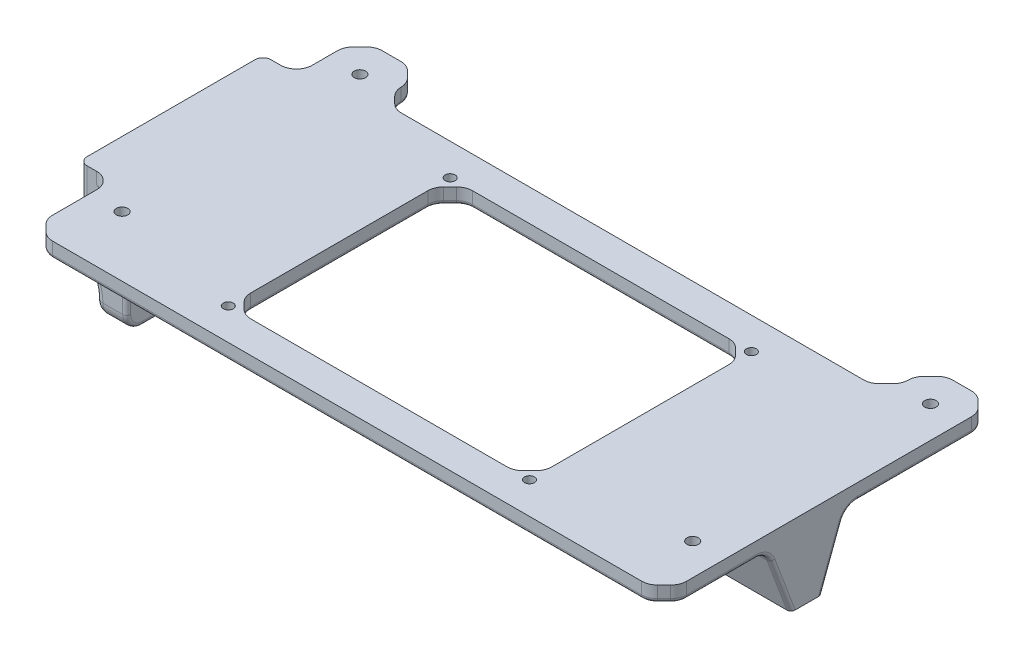
SolidWorks part; units mm, degrees
ref_plane "Front Plane" through (0, 0, 0) normal (0, 0, 1) x (1, 0, 0)
ref_plane "Top Plane" through (0, 0, 0) normal (0, 1, 0) x (1, 0, 0)
ref_plane "Right Plane" through (0, 0, 0) normal (1, 0, 0) x (0, 0, -1)
sketch "Sketch4" plane through (0, 0, 0) normal (0, 1, 0) x (1, 0, 0)
  line L1 (-47.5, 35) -> (47.5, 35) construction
  line L2 (-47.5, 35) -> (-47.5, -35) construction
  line L3 (-47.5, -35) -> (47.5, -35) construction
  line L4 (47.5, 35) -> (47.5, -35) construction
  line L5 (-100, -45) -> (100, -45)
  line L6 (-100, -45) -> (-100, 45)
  line L7 (-100, 45) -> (100, 45)
  line L8 (100, -45) -> (100, 45)
  line L9 (-100, -45) -> (100, 45) construction
  line L10 (-100, 45) -> (100, -45) construction
  point P4 (0, 0)
  dimension "D1" = 95
  dimension "D2" = 70
  dimension "D3" = 35
  dimension "D4" = 47.5
  dimension "D5" = 200
  dimension "D6" = 90
extrude "Boss-Extrude3" add sketch "Sketch4" along normal blind 5
sketch "Sketch5" plane through (0, 5, 0) normal (0, 1, 0) x (1, 0, 0)
  line L0 (-47.5, 30) -> (-42.5, 35)
  line L1 (-47.5, -35) -> (47.5, -35) construction
  line L2 (-47.5, -35) -> (-47.5, 35) construction
  line L3 (-47.5, 35) -> (47.5, 35) construction
  line L4 (47.5, -35) -> (47.5, 35) construction
  line L5 (-47.5, -35) -> (47.5, 35) construction
  line L6 (-47.5, 35) -> (47.5, -35) construction
  line L7 (-42.5, -35) -> (42.5, -35)
  line L8 (-47.5, -30) -> (-47.5, 30)
  line L9 (-42.5, 35) -> (42.5, 35)
  line L10 (47.5, -30) -> (47.5, 30)
  line L11 (-47.5, -35) -> (47.5, 35) construction
  line L12 (-47.5, 35) -> (47.5, -35) construction
  line L13 (42.5, 35) -> (47.5, 30)
  line L14 (42.5, -35) -> (47.5, -30)
  line L15 (-47.5, -30) -> (-42.5, -35)
  circle A0 centre (-47.5, 35) radius 1.575
  circle A1 centre (47.5, 35) radius 1.575
  circle A2 centre (-47.5, -35) radius 1.575
  circle A3 centre (47.5, -35) radius 1.575
  point P0 (0, 0)
  point P10 (0, 0)
  dimension "D3" = 3.15
  dimension "D4" = 3.15
  dimension "D5" = 3.15
  dimension "D6" = 3.15
  dimension "D1" = 95
  dimension "D2" = 70
extrude "Cut-Extrude1" cut sketch "Sketch5" against normal through all
sketch "Sketch6" plane through (0, 5, 0) normal (0, 1, 0) x (1, 0, 0)
  line L0 (100, 45) -> (-100, 45) construction
  line L1 (-82.55, -45) -> (82.55, -45) construction
  line L2 (-82.55, -45) -> (-82.55, 45) construction
  line L3 (-82.55, 45) -> (82.55, 45) construction
  line L4 (82.55, -45) -> (82.55, 45) construction
  line L5 (-82.55, -45) -> (82.55, 45) construction
  line L6 (-82.55, 45) -> (82.55, -45) construction
  line L7 (82.55, 0) -> (78.55, 0)
  line L8 (78.55, 0) -> (78.55, 5)
  line L9 (100, -45) -> (100, 45) construction
  line L10 (78.55, 5) -> (100, 5)
  line L11 (78.55, 5) -> (78.55, -5)
  line L12 (78.55, -5) -> (100, -5)
  line L13 (100, 5) -> (100, -5)
  point P0 (0, 0)
  dimension "D1" = 165.1
  dimension "D2" = 4
  dimension "D3" = 5
  dimension "D4" = 10
extrude "Boss-Extrude4" add sketch "Sketch6" along normal blind 20 contours L10 L13 L12 L11
sketch "Sketch8" plane through (78.55, 0, 0) normal (-1, 0, 0) x (0, 0, 1)
  line L0 (-5, 25) -> (5, 25) construction
  circle A0 centre (0, 25) radius 4
  dimension "D1" = 8
extrude "Cut-Extrude2" cut sketch "Sketch8" against normal blind 4.1
sketch "Sketch9" plane through (0, 25, 0) normal (0, 1, 0) x (1, 0, 0)
  line L0 (78.55, 0) -> (100, 0)
  line L1 (78.55, 5) -> (78.55, -5) construction
  line L2 (100, 5) -> (100, -5) construction
  circle A0 centre (87.5, 0) radius 1.8
  circle A1 centre (95, 0) radius 1.8
  dimension "D1" = 3.6
  dimension "D2" = 3.6
  dimension "D3" = 5
  dimension "D4" = 12.5
extrude "Cut-Extrude3" cut sketch "Sketch9" against normal blind 10 contours A0 | A1
sketch "Sketch10" plane through (0, 5, 0) normal (0, 1, 0) x (1, 0, 0)
  line L0 (100, 45) -> (-100, 45) construction
  line L1 (-82.55, -45) -> (82.55, -45) construction
  line L2 (-82.55, -45) -> (-82.55, 45) construction
  line L3 (-82.55, 45) -> (82.55, 45) construction
  line L4 (82.55, -45) -> (82.55, 45) construction
  line L5 (-82.55, -45) -> (82.55, 45) construction
  line L6 (-82.55, 45) -> (82.55, -45) construction
  line L7 (-82.55, 0) -> (-95.55, 0) construction
  line L8 (-95.55, 0) -> (-95.55, -38) construction
  line L10 (-95.55, -38) -> (-123.55, -38)
  line L11 (-95.55, -38) -> (-95.55, 22)
  line L12 (-95.55, 22) -> (-123.55, 22)
  line L13 (-123.55, -38) -> (-123.55, 22)
  point P0 (0, 0)
  dimension "D1" = 165.1
  dimension "D2" = 13
  dimension "D3" = 38
  dimension "D4" = 28
  dimension "D5" = 60
extrude "Boss-Extrude5" add sketch "Sketch10" along normal blind 20 contours L13 L12 L11 L10
sketch "Sketch12" plane through (0, 5, 0) normal (0, -1, 0) x (1, 0, 0)
  line L4 (-100, -22) -> (-100, 38)
  line L5 (-100, 38) -> (-123.55, 38)
  line L6 (-123.55, 38) -> (-123.55, -22)
  line L7 (-123.55, -22) -> (-100, -22)
  line L8 (-100, -22) -> (-100, 38)
  line L9 (-100, 38) -> (-123.55, 38)
  line L10 (-123.55, 38) -> (-123.55, -22)
  line L11 (-123.55, -22) -> (-100, -22)
  dimension "D1" = 0
extrude "Boss-Extrude6" add sketch "Sketch12" along normal up to surface (5 mm away) up to face at (47.5, 0, -33.425)
sketch "Sketch13" plane through (0, 25, 0) normal (0, 1, 0) x (1, 0, 0)
  line L0 (-95.55, -38) -> (-123.55, -38) construction
  line L1 (-95.55, 22) -> (-105.55, 22)
  line L2 (-95.55, 22) -> (-95.55, -38)
  line L3 (-95.55, -38) -> (-105.55, -38)
  line L4 (-105.55, 22) -> (-105.55, -38)
  dimension "D1" = 10
extrude "Boss-Extrude7" add sketch "Sketch13" along normal blind 15
sketch "Sketch14" plane through (-95.55, 0, 0) normal (1, 0, 0) x (0, 0, -1)
  line L1 (4, 25) -> (-4, 25)
  line L2 (4, 25) -> (-4, 25) construction
  line L3 (-30.5, 35.25) -> (10.5, 35.25)
  line L4 (-30.5, 35.25) -> (-30.5, 14.75)
  line L5 (-30.5, 14.75) -> (10.5, 14.75)
  line L6 (10.5, 35.25) -> (10.5, 14.75)
  arc A1 (-4, 25) -> (4, 25) centre (0, 25) ccw
  arc A2 (-4, 25) -> (4, 25) centre (0, 25) ccw construction
  dimension "D2" = 20.5
  dimension "D3" = 10.25
  dimension "D4" = 41
  dimension "D5" = 10.5
  dimension "D1" = 0
extrude "Cut-Extrude7" cut sketch "Sketch14" against normal through all contours L4 L5 L6 L3
sketch "Sketch15" plane through (0, 0, -22) normal (0, 0, -1) x (-1, 0, 0)
  line L8 (95.55, 5) -> (100, 5)
  line L9 (100, 5) -> (100, 0)
  line L10 (100, 0) -> (123.55, 0)
  line L11 (123.55, 0) -> (123.55, 25)
  line L12 (123.55, 25) -> (105.55, 25)
  line L13 (105.55, 25) -> (105.55, 40)
  line L14 (105.55, 40) -> (95.55, 40)
  line L15 (95.55, 40) -> (95.55, 5)
  line L16 (95.55, 5) -> (100, 5)
  line L17 (100, 5) -> (100, 0)
  line L18 (100, 0) -> (123.55, 0)
  line L19 (123.55, 0) -> (123.55, 25)
  line L20 (123.55, 25) -> (105.55, 25)
  line L21 (105.55, 25) -> (105.55, 40)
  line L22 (105.55, 40) -> (95.55, 40)
  line L23 (95.55, 40) -> (95.55, 5)
  dimension "D1" = 0
extrude "Cut-Extrude8" cut sketch "Sketch15" against normal blind 3
sketch "Sketch16" plane through (-95.55, 0, 0) normal (1, 0, 0) x (0, 0, -1)
  line L0 (-10, 35.25) -> (-10, 14.75) construction
  line L1 (-30.5, 35.25) -> (10.5, 35.25) construction
  line L2 (-30.5, 14.75) -> (10.5, 14.75) construction
  line L3 (-10, 25) -> (15.25, 25) construction
  line L4 (19, 5) -> (19, 40)
  line L5 (19, 40) -> (-38, 40)
  line L6 (-38, 40) -> (-38, 5)
  line L7 (-38, 5) -> (19, 5)
  line L8 (19, 5) -> (19, 40) construction
  line L9 (19, 40) -> (-38, 40) construction
  line L10 (-38, 40) -> (-38, 5) construction
  line L11 (-38, 5) -> (19, 5) construction
  line L12 (15.25, 25) -> (15.25, 30) construction
  circle A0 centre (15.25, 30) radius 1.8
  circle A1 centre (15.25, 20) radius 1.8
  circle A2 centre (-35.25, 20) radius 1.8
  circle A3 centre (-35.25, 30) radius 1.8
  dimension "D4" = 3.6
  dimension "D2" = 25.25
  dimension "D3" = 5
  dimension "D1" = 0
extrude "Cut-Extrude9" cut sketch "Sketch16" against normal blind 10
sketch "Sketch17" plane through (0, 0, 38) normal (0, 0, 1) x (1, 0, 0)
  line L8 (-100, 5) -> (-95.55, 5)
  line L9 (-95.55, 5) -> (-95.55, 40)
  line L10 (-95.55, 40) -> (-105.55, 40)
  line L11 (-105.55, 40) -> (-105.55, 25)
  line L12 (-105.55, 25) -> (-123.55, 25)
  line L13 (-123.55, 25) -> (-123.55, 0)
  line L14 (-123.55, 0) -> (-100, 0)
  line L15 (-100, 0) -> (-100, 5)
  line L16 (-100, 5) -> (-95.55, 5)
  line L17 (-95.55, 5) -> (-95.55, 40)
  line L18 (-95.55, 40) -> (-105.55, 40)
  line L19 (-105.55, 40) -> (-105.55, 25)
  line L20 (-105.55, 25) -> (-123.55, 25)
  line L21 (-123.55, 25) -> (-123.55, 0)
  line L22 (-123.55, 0) -> (-100, 0)
  line L23 (-100, 0) -> (-100, 5)
  dimension "D1" = 0
extrude "Boss-Extrude8" add sketch "Sketch17" along normal blind 1
sketch "Sketch19" plane through (-123.55, 0, 0) normal (-1, 0, 0) x (0, 0, 1)
  line L8 (-10.5, 25) -> (-19, 25)
  line L9 (-19, 25) -> (-19, 0)
  line L10 (-19, 0) -> (39, 0)
  line L11 (39, 0) -> (39, 25)
  line L12 (39, 25) -> (30.5, 25)
  line L13 (30.5, 25) -> (30.5, 14.75)
  line L14 (30.5, 14.75) -> (-10.5, 14.75)
  line L15 (-10.5, 14.75) -> (-10.5, 25)
  line L16 (-10.5, 25) -> (-19, 25)
  line L17 (-19, 25) -> (-19, 0)
  line L18 (-19, 0) -> (39, 0)
  line L19 (39, 0) -> (39, 25)
  line L20 (39, 25) -> (30.5, 25)
  line L21 (30.5, 25) -> (30.5, 14.75)
  line L22 (30.5, 14.75) -> (-10.5, 14.75)
  line L23 (-10.5, 14.75) -> (-10.5, 25)
  dimension "D1" = 0
extrude "Cut-Extrude10" cut sketch "Sketch19" against normal blind 13
fillet "Fillet1" radius 12.5 2 edges at (-105.55, 25, -14.75) (-105.55, 25, 34.75)
fillet "Fillet2" radius 5 2 edges at (-100.55, 40, 39) (-100.55, 40, -19)
fillet "Fillet3" radius 5 2 edges at (-110.55, 25, 34.75) (-110.55, 25, -14.75)
sketch "Sketch20" plane through (0, 5, 0) normal (0, 1, 0) x (1, 0, 0)
  line L1 (-100, -45) -> (-80, -45)
  line L2 (-100, -45) -> (-100, -59)
  line L3 (-100, -59) -> (-80, -59)
  line L4 (-80, -45) -> (-80, -59)
  line L5 (100, -45) -> (80, -45)
  line L6 (100, -45) -> (100, -59)
  line L7 (100, -59) -> (80, -59)
  line L8 (80, -45) -> (80, -59)
  dimension "D1" = 14
  dimension "D2" = 20
  dimension "D3" = 20
extrude "Boss-Extrude9" add sketch "Sketch20" against normal up to surface (5 mm away) up to face at (47.5, 0, -33.425)
sketch "Sketch21" plane through (0, 5, 0) normal (0, 1, 0) x (1, 0, 0)
  line L0 (100, 0) -> (100, 45)
  line L1 (100, 5) -> (100, -5) construction
  line L2 (100, 0) -> (100, -49)
  line L3 (-90, -59) -> (-90, -49) construction
  line L4 (-100, -59) -> (-80, -59) construction
  line L5 (-100, -39) -> (-95.55, -39) construction
  line L6 (100, -59) -> (100, -5) construction
  line L7 (0, 0) -> (0, -59) construction
  line L8 (-90, -49) -> (-90, 26) construction
  line L9 (82.55, 45) -> (-82.55, 45)
  line L10 (82.55, 45) -> (82.55, -45)
  line L11 (82.55, -45) -> (-82.55, -45)
  line L12 (-82.55, 45) -> (-82.55, -45)
  line L13 (82.55, 45) -> (-82.55, -45) construction
  line L14 (82.55, -45) -> (-82.55, 45) construction
  circle A0 centre (-90, -49) radius 1.8
  circle A1 centre (-90, 26) radius 1.8
  circle A2 centre (90, -49) radius 1.8
  circle A3 centre (90, 26) radius 1.8
  dimension "D1" = 3.6
  dimension "D5" = 3.6
  dimension "D2" = 10
  dimension "D3" = 165.1
  dimension "D4" = 75
extrude "Cut-Extrude11" cut sketch "Sketch21" against normal through all contours A1 | A0 | A3 | A2
chamfer "Chamfer1" distance 5 angle 45 8 edges at (100, 2.5, 59) (80, 2.5, 59) (80, 2.5, 45) (-80, 2.5, 45) (-80, 2.5, 59) (-100, 2.5, 59) (100, 2.5, -45) (-100, 2.5, -45)
fillet "Fillet4" radius 5 14 edges at (-75, 2.5, 45) (-85, 2.5, 59) (-95, 2.5, 59) (-100, 2.5, 54) (100, 2.5, 54) (95, 2.5, 59) (85, 2.5, 59) (80, 2.5, 50) (75, 2.5, 45) (100, 2.5, -40) (95, 2.5, -45) (-100, 2.5, -40) (-95, 2.5, -45) (-80, 2.5, 50)
fillet "Fillet5" radius 5 2 edges at (80, 2.5, 54) (-80, 2.5, 54)
fillet "Fillet6" radius 5 8 edges at (47.5, 2.5, -30) (42.5, 2.5, -35) (47.5, 2.5, 30) (42.5, 2.5, 35) (-42.5, 2.5, 35) (-47.5, 2.5, 30) (-42.5, 2.5, -35) (-47.5, 2.5, -30)
sketch "Sketch22" plane through (100, 0, 0) normal (1, 0, 0) x (0, 0, -1)
  line L0 (-5, 25) -> (-12.5, 5)
  line L1 (-51.9289, 5) -> (-5, 5) construction
  line L2 (-12.5, 5) -> (-5, 5)
  line L3 (-5, 5) -> (-5, 25)
  line L4 (0, 25) -> (0, 5) construction
  line L5 (5, 25) -> (-5, 25) construction
  line L6 (5, 5) -> (5, 25)
  line L7 (12.5, 5) -> (5, 5)
  line L8 (5, 25) -> (12.5, 5)
  dimension "D1" = 7.5
extrude "Boss-Extrude10" add sketch "Sketch22" against normal up to surface (21.45 mm away) up to face at (78.55, 17.6667, 0)
fillet "Fillet7" radius 5 2 edges at (89.275, 5, -12.5) (89.275, 5, 12.5)
fillet "Fillet9" radius 2.5 9 edges at (-110.55, 11.3763, -19) (-110.1791, 24.6424, -19) (-106.4772, 30.2754, -19) (-105.55, 38.5355, -17.5355) (-105.55, 40, 10) (-105.55, 38.5355, 37.5355) (-106.4772, 30.2754, 39) (-110.1791, 24.6424, 39) (-110.55, 11.3763, 39)
fillet "Fillet10" radius 5 2 edges at (-100, 2.5, 39) (-100, 2.5, -19)
fillet "Fillet11" radius 5 1 edges at (78.55, 5, 0)
fillet "Fillet12" radius 1.25 38 edges at (-101.4645, 5, 40.4645) (-100, 5, 47.9645) (-99.6194, 5, 53.8423) (-97.5, 5, 56.5) (-94.8423, 5, 58.6194) (-90, 5, 59) (-85.1577, 5, 58.6194) (-82.4995, 5, 56.4995) (-80.3934, 5, 53.8743) (-79.6056, 5, 50.1246) (-77.5, 5, 47.5) (-74.8423, 5, 45.3806) (100, 16.6222, 8.1417) (100, 5.8904, 13.117) (100, 5, 33.947) (99.6194, 5, 53.8423) (97.5, 5, 56.5) (94.8423, 5, 58.6194) (90, 5, 59) (85.1577, 5, 58.6194) (82.4995, 5, 56.4995) (80.3934, 5, 53.8743) (79.6056, 5, 50.1246) (77.5, 5, 47.5) (74.8423, 5, 45.3806) (100, 16.6222, -8.1417) (100, 5.8904, -13.117) (100, 5, -26.947) (99.6194, 5, -39.8423) (97.5, 5, -42.5) (94.8423, 5, -44.6194) (-101.4645, 5, -20.4645) (-100, 5, -30.9645) (-99.6194, 5, -39.8423) (-97.5, 5, -42.5) (-94.8423, 5, -44.6194) (0, 5, 45) (0, 5, -45)
fillet "Fillet13" radius 1.25 16 edges at (42.3423, 5, -34.6194) (45, 5, -32.5) (47.1194, 5, -29.8423) (47.5, 5, 0) (47.1194, 5, 29.8423) (45, 5, 32.5) (42.3423, 5, 34.6194) (0, 5, 35) (-42.3423, 5, 34.6194) (-45, 5, 32.5) (-47.1194, 5, 29.8423) (-47.5, 5, 0) (-47.1194, 5, -29.8423) (-45, 5, -32.5) (-42.3423, 5, -34.6194) (0, 5, -35)
fillet "Fillet14" radius 1.25 5 edges at (-95.55, 20, 39) (-95.55, 38.5355, 37.5355) (-95.55, 20, -19) (-95.55, 38.5355, -17.5355) (-95.55, 40, 10)
fillet "Fillet15" radius 1.25 14 edges at (-110.55, 18.7513, 30.5) (-105.55, 35.125, 30.5) (-106.4772, 30.2754, 30.5) (-105.55, 35.125, -10.5) (-106.4772, 30.2754, -10.5) (-110.1791, 24.6424, -10.5) (-95.55, 25, 30.5) (-95.55, 35.25, 10) (-95.55, 25, -10.5) (-95.55, 14.75, 10) (-110.55, 14.75, 10) (-110.1791, 24.6424, 30.5) (-105.55, 35.25, 10) (-110.55, 18.7513, -10.5)
ref_plane "Plane1" through (0, 0, 75) normal (0, 0, 1) x (1, 0, 0)
mirror "Mirror2" about plane through (0, 0, 75) normal (0, 0, 1) of bodies 127
sketch "Sketch23" plane through (0, 5, 0) normal (0, 1, 0) x (1, 0, 0)
  line L1 (-118.2086, -64.4154) -> (118.2086, -64.4154)
  line L2 (-118.2086, -64.4154) -> (-118.2086, 64.4154)
  line L3 (-118.2086, 64.4154) -> (118.2086, 64.4154)
  line L4 (118.2086, -64.4154) -> (118.2086, 64.4154)
  line L5 (-118.2086, -64.4154) -> (118.2086, 64.4154) construction
  line L6 (-118.2086, 64.4154) -> (118.2086, -64.4154) construction
  point P0 (0, 0)
  dimension "D1" = 236.4172
  dimension "D2" = 128.8308
extrude "Cut-Extrude12" cut sketch "Sketch23" against normal through all and the other way through all
ref_plane "Plane2" through (0, 70, 0) normal (0, 1, 0) x (1, 0, 0)
mirror "Mirror4" about plane through (0, 70, 0) normal (0, 1, 0) of bodies 128
sketch "Sketch24" plane through (0, 70, 0) normal (0, 1, 0) x (1, 0, 0)
  line L1 (-157.4168, -70.1279) -> (136.2709, -70.1279)
  line L2 (-157.4168, -70.1279) -> (-157.4168, -219.4707)
  line L3 (-157.4168, -219.4707) -> (136.2709, -219.4707)
  line L4 (136.2709, -70.1279) -> (136.2709, -219.4707)
extrude "Cut-Extrude13" cut sketch "Sketch24" against normal through all
